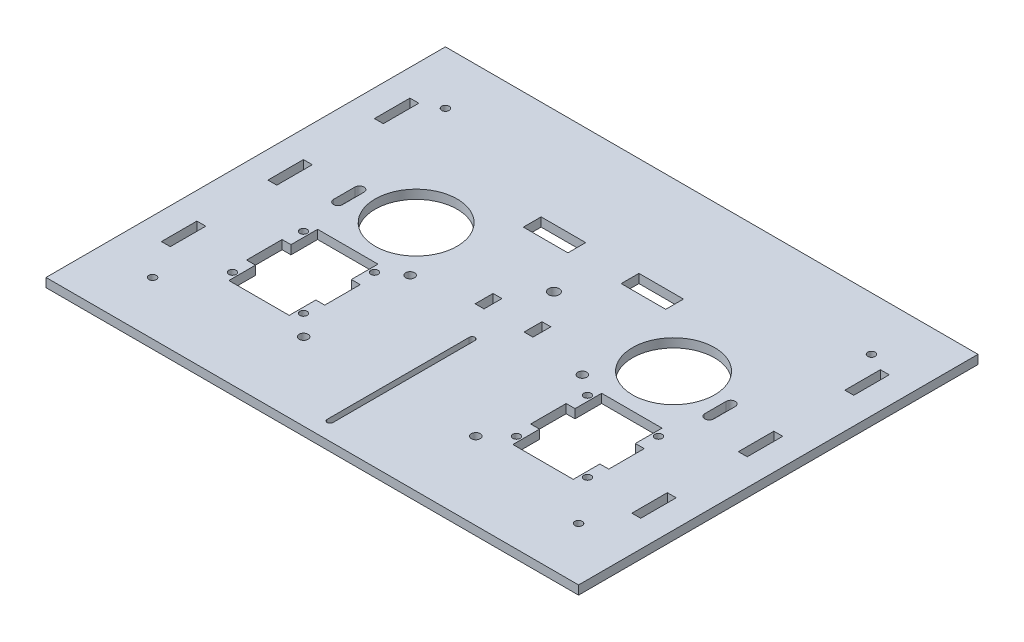
SolidWorks part; units mm, degrees
ref_plane "前基準面" through (0, 0, 0) normal (0, 0, 1) x (1, 0, 0)
ref_plane "上基準面" through (0, 0, 0) normal (0, 1, 0) x (1, 0, 0)
ref_plane "右基準面" through (0, 0, 0) normal (1, 0, 0) x (0, 0, -1)
sketch "草圖1" plane through (0, 0, 0) normal (0, 1, 0) x (1, 0, 0)
  line L0 (-130, 90) -> (130, 90) construction
  line L1 (-150, 100) -> (150, 100) construction
  line L2 (-150, 100) -> (-150, -100)
  line L3 (-150, -100) -> (150, -100) construction
  line L5 (0, 100) -> (0, -100) construction
  line L8 (-130, 100) -> (-110, 100) construction
  line L9 (-150, 100) -> (-150, -100) construction
  line L16 (-130, 100) -> (-130, -100) construction
  line L17 (-130, -100) -> (-110, -100) construction
  line L20 (-150, -100) -> (-150, -120)
  line L23 (-150, -100) -> (150, -100) construction
  line L35 (-110, 100) -> (-110, -100) construction
  line L38 (-110, 100) -> (110, 100) construction
  line L41 (-110, 100) -> (-110, 80) construction
  line L50 (-110, 80) -> (110, 80) construction
  line L59 (110, 100) -> (110, 80) construction
  line L65 (-150, -100) -> (150, -100) construction
  line L68 (150, -100) -> (150, 100)
  line L70 (-150, 100) -> (150, 100) construction
  line L73 (-150, 100) -> (-150, 105)
  line L77 (110, 100) -> (130, 100) construction
  line L80 (110, 100) -> (110, -100) construction
  line L83 (110, -100) -> (130, -100) construction
  line L86 (130, 100) -> (130, -100) construction
  line L89 (110, -100) -> (-110, -100) construction
  line L92 (110, -100) -> (110, -80) construction
  line L93 (-150, 100) -> (150, 100) construction
  line L97 (-150, 105) -> (150, 105)
  line L98 (150, 100) -> (150, 105)
  line L99 (-150, -120) -> (150, -120)
  line L100 (150, -120) -> (150, -100)
  line L108 (110, -80) -> (-110, -80) construction
  line L109 (-110, -100) -> (-110, -80) construction
  line L110 (130, -70) -> (135, -70)
  line L111 (-120, 100) -> (-120, -100) construction
  line L112 (-130, -90) -> (130, -90) construction
  line L113 (120, -100) -> (120, 100) construction
  line L114 (-130, 70) -> (-135, 70)
  line L115 (-130, 70) -> (-130, 50)
  line L116 (-130, 50) -> (-135, 50)
  line L117 (-135, 70) -> (-135, 50)
  line L118 (-130, 10) -> (-135, 10)
  line L119 (-130, 10) -> (-130, -10)
  line L120 (-130, -10) -> (-135, -10)
  line L121 (-135, 10) -> (-135, -10)
  line L122 (-130, -50) -> (-135, -50)
  line L123 (-130, -50) -> (-130, -70)
  line L124 (-130, -70) -> (-135, -70)
  line L125 (-135, -50) -> (-135, -70)
  line L126 (135, -50) -> (135, -70)
  line L127 (130, -50) -> (135, -50)
  line L128 (130, -50) -> (130, -70)
  line L129 (130, -10) -> (135, -10)
  line L130 (135, 10) -> (135, -10)
  line L131 (130, 10) -> (135, 10)
  line L132 (130, 10) -> (130, -10)
  line L133 (130, 50) -> (135, 50)
  line L134 (135, 70) -> (135, 50)
  line L135 (130, 70) -> (135, 70)
  line L136 (130, 70) -> (130, 50)
  circle A73 centre (-120, 75) radius 2.1
  circle A74 centre (120, 75) radius 2.1
  circle A75 centre (120, -90) radius 2.1
  circle A76 centre (-120, -90) radius 2.1
  point P6 (0, 0)
  point P9 (0, -80)
  point P18 (0, 0)
  point P24 (-140, 64.2857)
  point P47 (-140, 38.5714)
  point P54 (-140, 12.8571)
  point P61 (-140, -12.8571)
  point P71 (-140, -38.5714)
  point P78 (-140, -64.2857)
  dimension "D3" = 300
  dimension "D5" = 20
  dimension "D8" = 220
  dimension "D13" = 4.2
  dimension "D14" = 20
  dimension "D2" = 200
  dimension "D4" = 20
  dimension "D6" = 20
  dimension "D7" = 20
  dimension "D9" = 10
  dimension "D10" = 10
  dimension "D11" = 10
  dimension "D12" = 10
  dimension "D15" = 20
  dimension "D16" = 20
  dimension "D17" = 20
  dimension "D18" = 5
  dimension "D19" = 40
  dimension "D20" = 40
  dimension "D21" = 30
  dimension "D22" = 25
  dimension "D24" = 5
extrude "填料-伸長1" add sketch "草圖1" along normal blind 5
sketch "草圖2" plane through (0, 5, 0) normal (0, 1, 0) x (1, 0, 0)
  line L0 (0, 116.4556) -> (0, -113.9778) construction
  line L1 (115, 11) -> (30, 11) construction
  line L2 (-72.5, 53.5) -> (-72.5, -31.5) construction
  line L3 (-115, 11) -> (-30, 11) construction
  line L4 (72.5, 53.5) -> (72.5, -31.5) construction
  line L10 (7.5, -98.8861) -> (-7.5, -98.8861) construction
  line L15 (7.5, -98.8861) -> (7.5, -28.8861) construction
  line L16 (7.5, -28.8861) -> (-7.5, -28.8861) construction
  line L17 (-7.5, -98.8861) -> (-7.5, -28.8861) construction
  line L20 (-7.5, -28.8861) -> (7.5, -28.8861) construction
  line L35 (-110, 100) -> (-110, -100) construction
  line L36 (36, -91.3861) -> (-36, -91.3861) construction
  line L37 (36, -91.3861) -> (36, 18.6139) construction
  line L38 (36, 18.6139) -> (-36, 18.6139) construction
  line L39 (-36, -91.3861) -> (-36, 18.6139) construction
  line L40 (-105, -20) -> (-55, -20) construction
  line L41 (-105, -20) -> (-105, -70) construction
  line L42 (-55, -20) -> (-55, -70) construction
  line L43 (-97, -20) -> (-63, -20)
  line L46 (-97, -20) -> (-97, -70)
  line L49 (-97, -70) -> (-63, -70)
  line L60 (-7.5, -51.3861) -> (7.5, -51.3861)
  line L61 (-7.5, -51.3861) -> (-7.5, -76.3861)
  line L62 (-7.5, -76.3861) -> (7.5, -76.3861)
  line L63 (7.5, -51.3861) -> (7.5, -76.3861)
  line L64 (-63, -20) -> (-63, -70)
  line L67 (-105, -70) -> (-55, -70) construction
  line L72 (-150, 100) -> (150, 100) construction
  line L73 (-150, -100) -> (150, -100) construction
  line L74 (97, -20) -> (97, -70)
  line L75 (240, -96.3861) -> (-240, -96.3861) construction
  line L76 (240, -96.3861) -> (240, -16.3861) construction
  line L78 (-240, -96.3861) -> (-240, -16.3861) construction
  line L83 (0, -40.4951) -> (0, 39.5049) construction
  line L84 (-150, 100) -> (150, 100)
  line L85 (97, -70) -> (63, -70)
  line L86 (63, -20) -> (63, -70)
  line L87 (97, -20) -> (63, -20)
  line L88 (-7.5, -91.3861) -> (-7.5, -116.3861)
  line L89 (-7.5, -91.3861) -> (7.5, -91.3861)
  line L90 (7.5, -91.3861) -> (7.5, -116.3861)
  line L91 (-7.5, -116.3861) -> (7.5, -116.3861)
  line L92 (240, -16.3861) -> (-240, -16.3861) construction
  circle A0 centre (-72.5, 11) radius 42.5
  circle A1 centre (-72.5, 11) radius 22.1
  circle A2 centre (-87, 11) radius 2
  circle A3 centre (-58, 11) radius 2
  circle A4 centre (58, 11) radius 2
  circle A5 centre (87, 11) radius 2
  circle A6 centre (72.5, 11) radius 22.1
  circle A7 centre (72.5, 11) radius 42.5
  circle A11 centre (0, -86.3861) radius 1.25 construction
  circle A12 centre (0, -16.3861) radius 35 construction
  circle A13 centre (0, -41.3861) radius 1.25 construction
  circle A28 centre (60, -65) radius 2.05
  circle A36 centre (-100, -25) radius 2.05
  circle A37 centre (-60, -25) radius 2.05
  circle A38 centre (-100, -65) radius 2.05
  circle A39 centre (-60, -65) radius 2.05
  circle A40 centre (100, -65) radius 2.05
  circle A41 centre (60, -25) radius 2.05
  circle A42 centre (100, -25) radius 2.05
  circle A43 centre (0, -56.3861) radius 35 construction
  point P29 (0, 18.6139)
  point P46 (-7.5, -63.8861)
  point P57 (-7.5, -63.8861)
  point P85 (-96.5, 66.7857)
  point P90 (-141.5, 66.7857)
  point P91 (-140, 13.2857)
  point P92 (-140, 68.2857)
  point P116 (0, -98.8861)
  point P142 (0, -96.3861)
  point P143 (0, 53.9014)
  dimension "D1" = 85
  dimension "D2" = 44.2
  dimension "D4" = 4
  dimension "D8" = 72
  dimension "D10" = 89
  dimension "D7" = 2
  dimension "D16" = 70
  dimension "D13" = 2.5
  dimension "D17" = 2
  dimension "D24" = 45
  dimension "D25" = 4.1
  dimension "D33" = 8
  dimension "D3" = 29
  dimension "D5" = 60
  dimension "D6" = 12.5
  dimension "D9" = 25
  dimension "D11" = 70
  dimension "D12" = 110
  dimension "D14" = 5
  dimension "D15" = 5
  dimension "D18" = 40
  dimension "D19" = 40
  dimension "D20" = 45
  dimension "D21" = 34
  dimension "D23" = 30
  dimension "D26" = 2
  dimension "D27" = 40
  dimension "D29" = 55
  dimension "D30" = 50
  dimension "D31" = 15
  dimension "D32" = 40
  dimension "D40" = 5
  dimension "D41" = 5
  dimension "D42" = 50
  dimension "D43" = 80
  dimension "D44" = 480
sketch "草圖3" plane through (0, 5, 0) normal (0, 1, 0) x (1, 0, 0)
  line L0 (0, 200116.4556) -> (0, -200113.9778) construction
  line L1 (0, 200116.4556) -> (0, -200113.9778) construction
  line L2 (0, 100) -> (0, -100) construction
  line L3 (-41, -6.3861) -> (-56, -6.3861) construction
  line L4 (-41, -6.3861) -> (-41, -26.3861) construction
  line L5 (-41, -26.3861) -> (-56, -26.3861) construction
  line L6 (-56, -6.3861) -> (-56, -26.3861) construction
  line L7 (0, 0) -> (0, 42.1207) construction
  line L8 (41, -26.3861) -> (56, -26.3861) construction
  line L9 (-7.5, -98.8861) -> (-7.5, -28.8861) construction
  line L10 (7.5, -28.8861) -> (-7.5, -28.8861) construction
  line L11 (7.5, -28.8861) -> (7.5, -18.8861) construction
  line L12 (7.5, -18.8861) -> (-7.5, -18.8861) construction
  line L13 (-7.5, -28.8861) -> (-7.5, -18.8861) construction
  line L14 (41, -6.3861) -> (41, -26.3861) construction
  line L15 (56, -6.3861) -> (56, -26.3861) construction
  line L16 (41, -6.3861) -> (56, -6.3861) construction
  line L17 (-97, -70) -> (-63, -70) construction
  line L18 (-63, -20) -> (-63, -70) construction
  line L19 (-97, -20) -> (-63, -20) construction
  line L20 (-97, -20) -> (-97, -70) construction
  line L21 (-97, -70) -> (-63, -70)
  line L22 (-63, -20) -> (-63, -35)
  line L23 (-97, -20) -> (-63, -20)
  line L24 (-97, -20) -> (-97, -35)
  line L25 (97, -20) -> (97, -35)
  line L26 (97, -20) -> (63, -20)
  line L27 (63, -20) -> (63, -35)
  line L28 (97, -70) -> (63, -70)
  line L29 (36, 18.6139) -> (-36, 18.6139) construction
  line L30 (-11.275, 23.1139) -> (11.275, 23.1139) construction
  line L31 (-11.275, 23.1139) -> (-11.275, -13.8861) construction
  line L32 (-11.275, -13.8861) -> (11.275, -13.8861) construction
  line L33 (11.275, 23.1139) -> (11.275, -13.8861) construction
  line L34 (-11.275, -1.8861) -> (-16.275, -1.8861)
  line L35 (-11.275, -1.8861) -> (-11.275, -11.9861)
  line L36 (-11.275, -11.9861) -> (-16.275, -11.9861)
  line L37 (-16.275, -1.8861) -> (-16.275, -11.9861)
  line L38 (11.275, -1.8861) -> (16.275, -1.8861)
  line L39 (11.275, -1.8861) -> (11.275, -11.9861)
  line L40 (11.275, -11.9861) -> (16.275, -11.9861)
  line L41 (16.275, -1.8861) -> (16.275, -11.9861)
  line L42 (-1.6, -70) -> (1.6, -70) construction
  line L43 (0, -30) -> (0, -110) construction
  line L44 (1.6, -30) -> (1.6, -110)
  line L45 (-1.6, -30) -> (-1.6, -110)
  line L46 (63, -55) -> (58, -55)
  line L47 (-97, -35) -> (-102, -35)
  line L49 (-97, -55) -> (-102, -55)
  line L50 (-102, -35) -> (-102, -55)
  line L51 (-63, -35) -> (-58, -35)
  line L53 (-63, -55) -> (-58, -55)
  line L54 (-58, -35) -> (-58, -55)
  line L55 (58, -35) -> (58, -55)
  line L56 (63, -35) -> (58, -35)
  line L58 (97, -55) -> (102, -55)
  line L59 (102, -35) -> (102, -55)
  line L60 (97, -35) -> (102, -35)
  line L62 (-97, -55) -> (-97, -70)
  line L63 (-63, -55) -> (-63, -70)
  line L64 (63, -55) -> (63, -70)
  line L65 (97, -55) -> (97, -70)
  line L66 (-80, -20) -> (-80, -70) construction
  line L68 (-150, -120) -> (150, -120) construction
  arc A0 (1.6, -30) -> (-1.6, -30) centre (0, -30) ccw
  arc A2 (-1.6, -110) -> (1.6, -110) centre (0, -110) ccw
  circle A4 centre (120, -90) radius 2.1 construction
  circle A6 centre (120, -90) radius 2.1 construction
  circle A10 centre (-48.5, -16.3861) radius 2.5
  circle A11 centre (48.5, -16.3861) radius 2.5
  circle A12 centre (48.5, -76.3861) radius 2.5
  circle A13 centre (-48.5, -76.3861) radius 2.5
  circle A14 centre (-72.5, 11) radius 22.1 construction
  circle A15 centre (-72.5, 11) radius 22.1 construction
  circle A16 centre (72.5, 11) radius 22.1 construction
  circle A17 centre (72.5, 11) radius 22.1 construction
  circle A18 centre (-72.5, 11) radius 23.1
  circle A19 centre (72.5, 11) radius 23.1
  circle A20 centre (0, 16.1139) radius 3
  circle A21 centre (0, -23.8861) radius 2 construction
  circle A22 centre (-100, -65) radius 2.05 construction
  circle A23 centre (-60, -65) radius 2.05 construction
  circle A24 centre (-60, -25) radius 2.05 construction
  circle A25 centre (-100, -25) radius 2.05 construction
  circle A26 centre (-100, -65) radius 2.05
  circle A27 centre (-60, -65) radius 2.05
  circle A28 centre (-60, -25) radius 2.05
  circle A29 centre (-100, -25) radius 2.05
  circle A30 centre (100, -25) radius 2.05
  circle A31 centre (60, -25) radius 2.05
  circle A32 centre (60, -65) radius 2.05
  circle A33 centre (100, -65) radius 2.05
  circle A34 centre (0, -106.6) radius 1.6 construction
  circle A35 centre (0, -33.4) radius 1.6 construction
  point P1 (0, -70)
  point P29 (-56, -16.3861)
  point P32 (-48.5, -26.3861)
  point P62 (-7.5, -23.8861)
  point P64 (0, 23.1139)
  point P107 (-102, -45)
  point P108 (0, -75.9735)
  point P109 (0, -71.5534)
  point P120 (-80, -45)
  dimension "D2" = 5
  dimension "D8" = 6
  dimension "D11" = 4
  dimension "D7" = 1
  dimension "D20" = 1
  dimension "D21" = 5
  dimension "D26" = 50
  dimension "D3" = 15
  dimension "D4" = 20
  dimension "D5" = 2
  dimension "D6" = 60
  dimension "D9" = 40
  dimension "D10" = 10
  dimension "D12" = 112
  dimension "D13" = 25
  dimension "D14" = 22.55
  dimension "D15" = 37
  dimension "D16" = 7
  dimension "D17" = 5
  dimension "D18" = 10.1
  dimension "D19" = 25
  dimension "D22" = 3.2
  dimension "D23" = 20
  dimension "D24" = 80
  dimension "D25" = 73.2
extrude "除料-伸長1" cut sketch "草圖3" against normal through all
sketch "草圖5" plane through (0, 5, 0) normal (0, 1, 0) x (1, 0, 0)
  line L0 (-150, 39) -> (150, 39) construction
  line L1 (-150, 105) -> (-150, -120) construction
  line L2 (150, -120) -> (150, 105) construction
  line L3 (-144.2587, 49) -> (142.9694, 49) construction
  line L4 (-150, 100) -> (-150, 105) construction
  line L5 (0, 36.1139) -> (0, 16.1139) construction
  line L8 (-0.85, 16.1139) -> (0.85, 16.1139) construction
  line L9 (-0.85, 18.0139) -> (0.85, 18.0139) construction
  line L10 (-0.85, 14.2139) -> (0.85, 14.2139) construction
  line L11 (5.05, 36.1139) -> (5.05, 16.1139) construction
  line L12 (-5.05, 36.1139) -> (-5.05, 16.1139) construction
  line L13 (0, 0) -> (0, 152.3042) construction
  line L14 (-15, 49) -> (15, 49) construction
  line L15 (-15, 49) -> (-15, 39) construction
  line L16 (-15, 39) -> (15, 39) construction
  line L17 (15, 49) -> (15, 39) construction
  line L18 (15, 39) -> (40.1, 39)
  line L19 (-15, 49) -> (-40.1, 49)
  line L20 (-15, 49) -> (-15, 39)
  line L21 (-15, 39) -> (-40.1, 39)
  line L22 (-40.1, 49) -> (-40.1, 39)
  line L23 (40.1, 49) -> (40.1, 39)
  line L24 (15, 49) -> (40.1, 49)
  line L25 (15, 49) -> (15, 39)
  line L26 (-150, 100) -> (150, 100) construction
  line L27 (-150, 100) -> (150, 100) construction
  line L28 (-104.55, 11.15) -> (-104.55, -0.95) construction
  line L31 (-102, 11.15) -> (-102, -0.95)
  line L32 (-130, 70) -> (-110, 70) construction
  line L33 (-130, 70) -> (-130, 30.1754) construction
  line L34 (-130, 30.1754) -> (-110, 30.1754) construction
  line L35 (-110, 70) -> (-110, 30.1754) construction
  line L36 (0, 100) -> (0, -100) construction
  line L39 (-98.5, 39) -> (-46.5, 39) construction
  line L40 (-98.5, 39) -> (-98.5, 37) construction
  line L41 (-98.5, 37) -> (-46.5, 37) construction
  line L42 (-46.5, 39) -> (-46.5, 37) construction
  line L43 (-111.8, 63.9563) -> (-99.5, 63.9563) construction
  line L44 (-111.8, 63.9563) -> (-111.8, -8.5) construction
  line L45 (-111.8, -8.5) -> (-99.5, -8.5) construction
  line L46 (-99.5, 63.9563) -> (-99.5, -8.5) construction
  line L47 (-107.1, 11.15) -> (-107.1, -0.95)
  line L48 (104.55, 11.15) -> (104.55, -0.95) construction
  line L49 (102, 11.15) -> (102, -0.95)
  line L50 (107.1, 11.15) -> (107.1, -0.95)
  circle A0 centre (0, 16.1139) radius 3 construction
  circle A1 centre (0, 16.1139) radius 3 construction
  circle A4 centre (0, 36.1139) radius 2.05 construction
  arc A5 (-0.85, 18.0139) -> (-0.85, 14.2139) centre (-0.85, 16.1139) ccw construction
  arc A6 (0.85, 14.2139) -> (0.85, 18.0139) centre (0.85, 16.1139) ccw construction
  arc A7 (5.05, 36.1139) -> (-5.05, 36.1139) centre (0, 36.1139) ccw construction
  arc A8 (-5.05, 16.1139) -> (5.05, 16.1139) centre (0, 16.1139) ccw construction
  arc A13 (-102, 11.15) -> (-107.1, 11.15) centre (-104.55, 11.15) ccw
  arc A14 (-107.1, -0.95) -> (-102, -0.95) centre (-104.55, -0.95) ccw
  arc A15 (-107.1, 11.15) -> (-102, 11.15) centre (-104.55, 11.15) ccw construction
  arc A16 (-102, -0.95) -> (-107.1, -0.95) centre (-104.55, -0.95) ccw construction
  arc A17 (102, 11.15) -> (107.1, 11.15) centre (104.55, 11.15) cw
  arc A18 (107.1, -0.95) -> (102, -0.95) centre (104.55, -0.95) cw
  point P3 (0, 26.1139)
  point P18 (0, 11.0639)
  point P19 (0, 41.1639)
  point P24 (0, 16.1139)
  point P29 (-2.75, 16.1139)
  point P30 (2.75, 16.1139)
  point P38 (0, 49)
  point P46 (-104.55, 5.1)
  point P51 (-104.55, -3.5)
  point P57 (-105.65, 66.45)
  point P79 (-104.55, 1.6)
  point P80 (-104.55, 8.6)
  point P84 (104.55, 5.1)
  dimension "D1" = 20
  dimension "D2" = 4.1
  dimension "D12" = 5.1
  dimension "D19" = 7
  dimension "D3" = 10
  dimension "D4" = 61
  dimension "D5" = 30.1
  dimension "D6" = 5.5
  dimension "D7" = 3.8
  dimension "D8" = 30
  dimension "D9" = 25.1
  dimension "D10" = 5
  dimension "D11" = 2.5
  dimension "D13" = 20
  dimension "D14" = 1
  dimension "D15" = 12.3
  dimension "D16" = 52
  dimension "D17" = 51.5
  dimension "D18" = 2
  dimension "D20" = 47.5
  dimension "D21" = 12.1
extrude "除料-伸長5" cut sketch "草圖5" against normal through all
